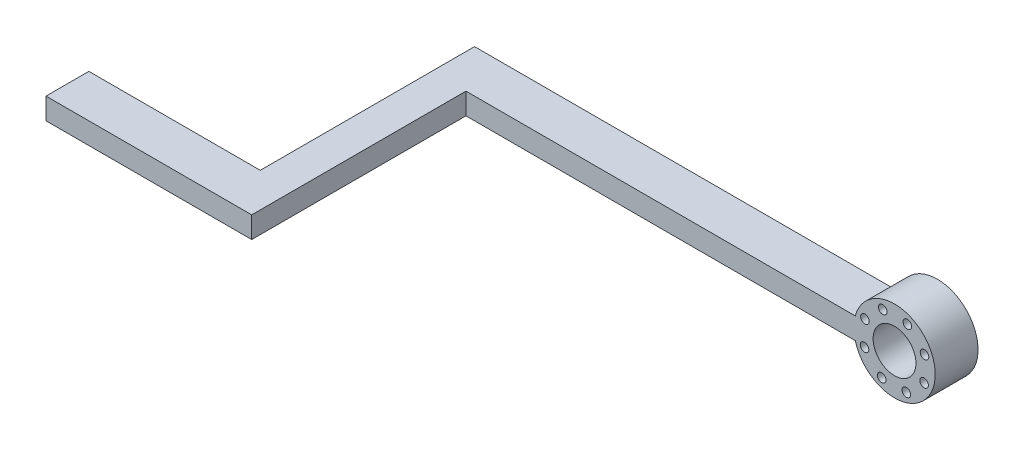
SolidWorks part; units mm, degrees
ref_plane "Front Plane" through (0, 0, 0) normal (0, 0, 1) x (1, 0, 0)
ref_plane "Top Plane" through (0, 0, 0) normal (0, 1, 0) x (1, 0, 0)
ref_plane "Right Plane" through (0, 0, 0) normal (1, 0, 0) x (0, 0, -1)
sketch "Sketch1" plane through (0, 0, 0) normal (0, 0, 1) x (1, 0, 0)
  line L0 (-9.1652, 2.5) -> (-100, 2.5)
  line L1 (-100, 2.5) -> (-100, -2.5)
  line L2 (-100, -2.5) -> (-9.1652, -2.5)
  arc A0 (-9.1652, -2.5) -> (-9.1652, 2.5) centre (0, 0) ccw
  circle A1 centre (0, 0) radius 5
  circle A2 centre (2.7554, -7) radius 1
  circle A3 centre (-3.0014, -6.8981) radius 1
  circle A4 centre (-7, -2.7554) radius 1
  circle A5 centre (-6.8981, 3.0014) radius 1
  circle A6 centre (-2.7554, 7) radius 1
  circle A7 centre (3.0014, 6.8981) radius 1
  circle A8 centre (7, 2.7554) radius 1
  circle A9 centre (6.8981, -3.0014) radius 1
  point P5 (-100, 0)
  point P26 (0, 0)
  dimension "D1" = 9.5
  dimension "D4" = 10
  dimension "D5" = 2
  dimension "D2" = 100
  dimension "D3" = 5
  dimension "D7" = 7
  dimension "D6" = 8
extrude "Boss-Extrude1" add sketch "Sketch1" along normal blind 10
sketch "Sketch2" plane through (0, 0, 10) normal (0, 0, 1) x (1, 0, 0)
  line L0 (-100, -2.5) -> (-9.1652, -2.5) construction
  line L1 (-100, 2.5) -> (-108, 2.5)
  line L2 (-100, 2.5) -> (-100, -2.5)
  line L3 (-100, -2.5) -> (-108, -2.5)
  line L4 (-108, 2.5) -> (-108, -2.5)
  dimension "D1" = 8
extrude "Boss-Extrude2" add sketch "Sketch2" against normal up to surface (10 mm away) and the other way blind 40 up to face at (-49.9163, 0, 0)
sketch "Sketch3" plane through (-108, 0, 0) normal (-1, 0, 0) x (0, 0, 1)
  line L0 (50, 2.5) -> (0, 2.5) construction
  line L1 (50, -2.5) -> (60, -2.5)
  line L2 (50, -2.5) -> (50, 2.5)
  line L3 (50, 2.5) -> (60, 2.5)
  line L4 (60, -2.5) -> (60, 2.5)
  dimension "D1" = 10
extrude "Boss-Extrude3" add sketch "Sketch3" against normal up to surface (8 mm away) and the other way blind 40 up to face at (-100, 0, 30)
